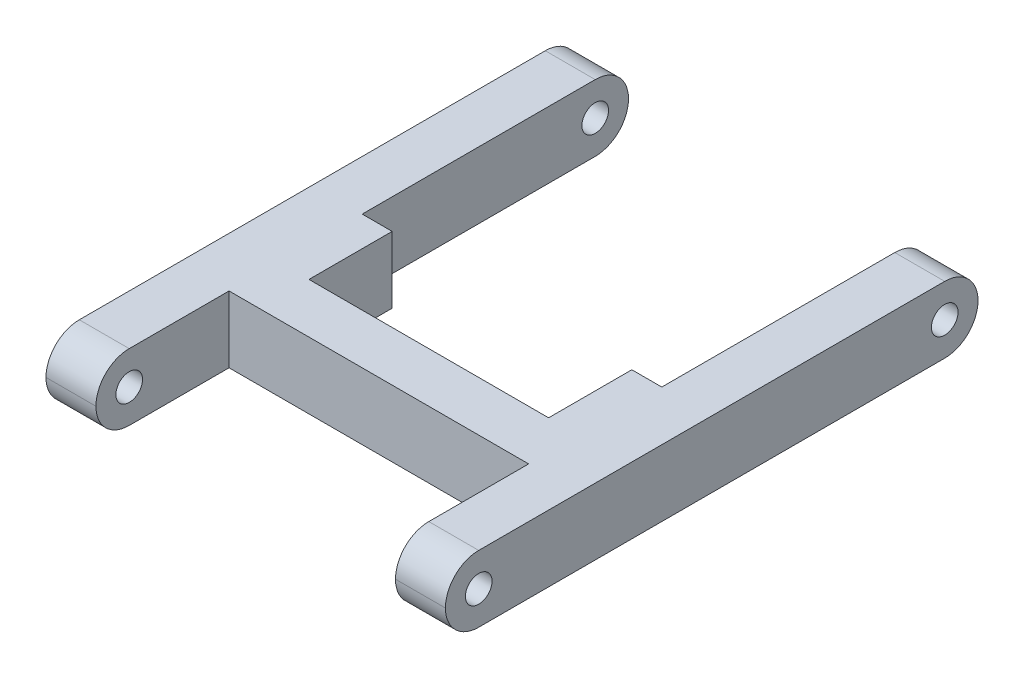
SolidWorks part; units mm, degrees
material "Alumina"
ref_plane "Front Plane" through (0, 0, 0) normal (0, 0, 1) x (1, 0, 0)
ref_plane "Top Plane" through (0, 0, 0) normal (0, 1, 0) x (1, 0, 0)
ref_plane "Right Plane" through (0, 0, 0) normal (1, 0, 0) x (0, 0, -1)
sketch "Sketch1" plane through (0, 0, 0) normal (0, 1, 0) x (1, 0, 0)
  line L0 (-30, 40) -> (-25.5, 40)
  line L1 (-30, -40) -> (30, -40)
  line L2 (-30, -40) -> (-30, 40)
  line L3 (-30, 40) -> (30, 40)
  line L4 (30, -40) -> (30, 40)
  line L5 (-30, -40) -> (30, 40) construction
  line L6 (-30, 40) -> (30, -40) construction
  line L8 (-25.5, 40) -> (26.5, 40)
  line L9 (-25.5, 40) -> (-25.5, 15)
  line L10 (-25.5, 15) -> (26.5, 15)
  line L11 (26.5, 40) -> (26.5, 15)
  point P0 (0, 0)
  dimension "D1" = 60
  dimension "D2" = 80
  dimension "D3" = 4.5
  dimension "D4" = 52
  dimension "D5" = 25
extrude "Boss-Extrude1" add sketch "Sketch1" along normal blind 10 contours L2 L1 L4 L3
sketch "Sketch3" plane through (0, 10, 0) normal (0, 1, 0) x (1, 0, 0)
  line L0 (-30, 40) -> (-22.5, 40)
  line L1 (-30, 40) -> (30, 40) construction
  line L2 (22.5, 40) -> (30, 40)
  line L3 (-22.5, 40) -> (22.5, 40)
  line L4 (-22.5, 40) -> (-22.5, 0)
  line L5 (-22.5, 0) -> (22.5, 0)
  line L6 (22.5, 40) -> (22.5, 0)
  dimension "D1" = 7.5
  dimension "D2" = 7.5
  dimension "D3" = 40
extrude "Cut-Extrude1" cut sketch "Sketch3" against normal through all contours L4 L3 L6 L5
sketch "Sketch4" plane through (0, 10, 0) normal (0, 1, 0) x (1, 0, 0)
  line L0 (-30, -40) -> (-22.5, -40)
  line L1 (-30, -40) -> (30, -40) construction
  line L2 (22.5, -40) -> (30, -40)
  line L3 (-22.5, -40) -> (22.5, -40)
  line L4 (-22.5, -40) -> (-22.5, -20)
  line L5 (-22.5, -20) -> (22.5, -20)
  line L6 (22.5, -40) -> (22.5, -20)
  dimension "D1" = 7.5
  dimension "D2" = 7.5
  dimension "D3" = 20
extrude "Cut-Extrude2" cut sketch "Sketch4" against normal through all contours L4 L3 L6 L5
sketch "Sketch5" plane through (-30, 0, 0) normal (-1, 0, 0) x (0, 0, 1)
  line L0 (-40, 10) -> (-30, 0) construction
  line L1 (40, 0) -> (-40, 0) construction
  line L2 (0, 0) -> (0, 10) construction
  line L3 (40, 10) -> (-40, 10) construction
  circle A0 centre (-35, 5) radius 2
  circle A1 centre (35, 5) radius 2
  dimension "D1" = 4
extrude "Cut-Extrude3" cut sketch "Sketch5" against normal through all contours A1 | A0 region at (-30, 5, 35)
fillet "Fillet1" radius 5 8 edges at (26.25, 0, 40) (-26.25, 0, 40) (-26.25, 0, -40) (26.25, 0, -40) (-26.25, 10, -40) (-26.25, 10, 40) (26.25, 10, 40) (26.25, 10, -40)
sketch "Sketch6" plane through (0, 10, 0) normal (0, 1, 0) x (1, 0, 0)
  line L1 (-18, 12.5) -> (18, 12.5)
  line L2 (-18, 12.5) -> (-18, -12.5)
  line L3 (-18, -12.5) -> (18, -12.5)
  line L4 (18, 12.5) -> (18, -12.5)
  line L5 (-18, 12.5) -> (18, -12.5) construction
  line L6 (-18, -12.5) -> (18, 12.5) construction
  point P0 (0, 0)
  dimension "D1" = 25
extrude "Cut-Extrude4" cut sketch "Sketch6" against normal through all contours L4 L1 L2 L3 | L2 L1 L4 L3 region at (0, 10, 0)
